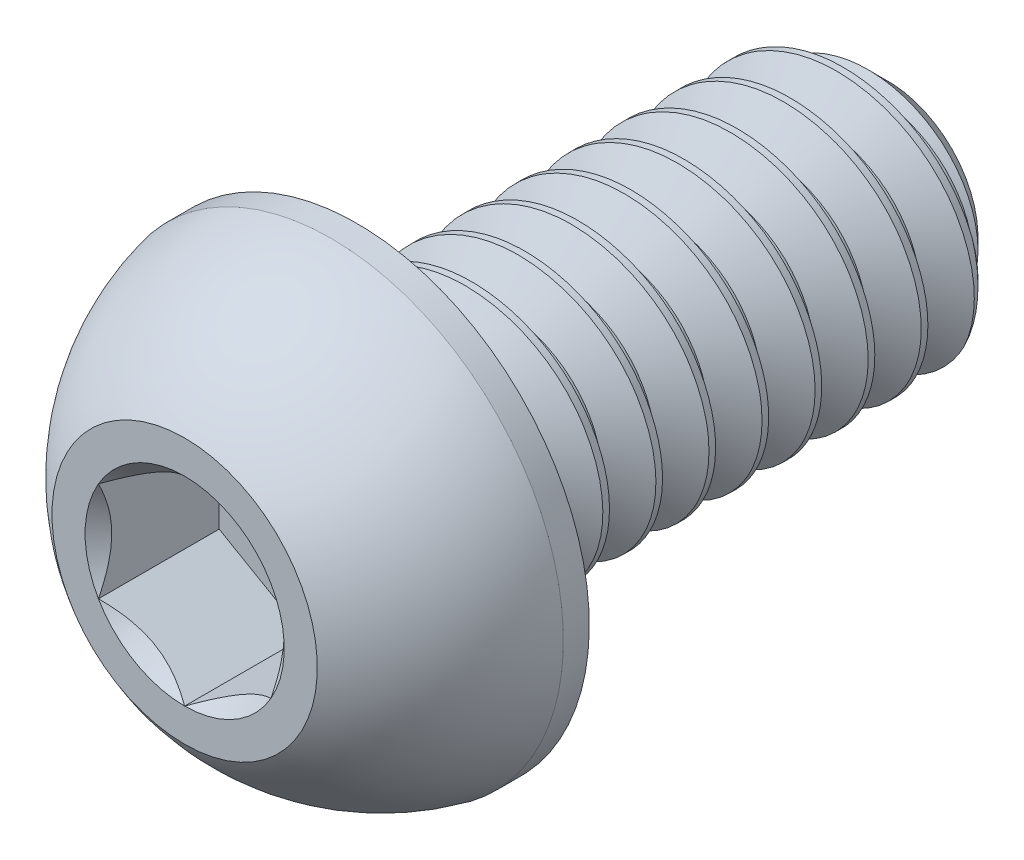
SolidWorks part; units mm, degrees
ref_plane "Front Plane" through (0, 0, 0) normal (0, 0, 1) x (1, 0, 0)
ref_plane "Top Plane" through (0, 0, 0) normal (0, 1, 0) x (1, 0, 0)
ref_plane "Right Plane" through (0, 0, 0) normal (1, 0, 0) x (0, 0, -1)
sketch "Sketch1" plane through (0, 0, 0) normal (1, 0, 0) x (0, 0, -1)
  line L0 (-2.65, 0) -> (2.65, 0) construction
  line L1 (-1.35, 1.75) -> (-1.35, -1.75) construction
  line L2 (2.65, 1) -> (2.65, -1) construction
  line L3 (2.625, 1.0433) -> (2.825, 0.6969) construction
  line L4 (2.825, 0.6969) -> (3.025, 1.0433) construction
  line L5 (3.025, 1.0433) -> (2.625, 1.0433) construction
  line L6 (2.65, 1) -> (3, 1) construction
  line L7 (2.825, 1.0433) -> (2.825, 1) construction
  line L8 (2.825, 1) -> (2.825, 0.7402) construction
  line L9 (2.825, 0.7402) -> (2.825, 0.6969) construction
  line L10 (2.8, 0.7402) -> (2.85, 0.7402)
  line L11 (2.6375, 1.0217) -> (3.0125, 1.0217)
  line L12 (2.85, 0.7402) -> (3.0125, 1.0217)
  line L13 (2.8, 0.7402) -> (2.6375, 1.0217)
  line L14 (-2.65, 0.65) -> (-2.65, -0.65) construction
  line L15 (2.65, 1) -> (-1.35, 1) construction
  point P3 (-1.35, 0)
  point P6 (-1.74, 0)
  point P21 (2.825, 1.0217)
  point P24 (-1.545, 1.75)
  point P25 (1.65, -1)
  point P26 (-2.65, 1)
  dimension "Head Height" = 1.3
  dimension "Length" = 4
  dimension "Head Dia" = 3.5
  dimension "Thread Dia" = 2
  dimension "Pitch" = 0.4
  dimension "D2" = 0.05
  dimension "Drive Size" = 1.3
  dimension "D1" = 0.91
  dimension "D3" = 0.195
  dimension "D4" = 1
sketch "Sketch2" plane through (0, 0, 0) normal (1, 0, 0) x (0, 0, -1)
  line L0 (-2.65, 0) -> (2.65, 0)
  line L1 (2.65, 0) -> (2.65, 0.68)
  line L2 (2.65, 1) -> (2.65, -1) construction
  line L3 (2.65, 0.68) -> (2.33, 1)
  line L4 (2.33, 1) -> (-1.35, 1)
  line L5 (-1.35, 1.75) -> (-1.35, -1.75) construction
  line L6 (-1.35, 1) -> (-1.35, 1.75)
  line L7 (-1.35, 1.75) -> (-1.545, 1.75)
  line L8 (2.65, 1) -> (3, 1) construction
  line L9 (-2.65, 0) -> (-2.65, 1)
  arc A0 (-2.65, 1) -> (-1.545, 1.75) centre (-1.1642, 0) cw
  dimension "D1" = 0.32
  dimension "D2" = 45
revolve "Revolve1" add sketch "Sketch2" angle 360 about L0
sketch "Sketch3" plane through (0, 0, 2.65) normal (0, 0, 1) x (1, 0, 0)
  line L1 (0, 0.7506) -> (-0.65, 0.3753)
  line L2 (-0.65, 0.3753) -> (-0.65, -0.3753)
  line L3 (-0.65, -0.3753) -> (0, -0.7506)
  line L4 (0, -0.7506) -> (0.65, -0.3753)
  line L5 (0.65, -0.3753) -> (0.65, 0.3753)
  line L6 (0.65, 0.3753) -> (0, 0.7506)
  circle A0 centre (0, 0) radius 0.65 construction
  dimension "D1" = 1.3
extrude "Cut-Extrude1" cut sketch "Sketch3" against normal up to vertex (0.91 mm away) up to point (0, 0, 1.74)
sketch "Sketch4" plane through (0, 0, 2.65) normal (0, 0, 1) x (1, 0, 0)
  circle A0 centre (0, 0) radius 0.7506
extrude "Cut-Extrude2" cut sketch "Sketch4" against normal blind 10 draft 45
split "Split1" bodies to split 106 resulting bodies 107 108 split by face at (0, -1.75, 1.35)
sketch "Sketch5" plane through (0, 0, -2.65) normal (0, 0, -1) x (-1, 0, 0)
  circle A0 centre (0, 0) radius 1 construction
  circle A1 centre (0, 0) radius 1
curve "Helix/Spiral1" pitch 0.4 height 4.4 radius 1 centre (0, 0, -2.65) axis (0, 0, 1) start towards (0, 1, 0)
sketch "Sketch6" plane through (0, 0, 0) normal (1, 0, 0) x (0, 0, -1)
  line L0 (2.8, 0.7402) -> (2.85, 0.7402) construction
  line L1 (2.8, 0.7402) -> (2.6375, 1.0217) construction
  line L2 (2.6375, 1.0217) -> (3.0125, 1.0217) construction
  line L3 (2.85, 0.7402) -> (3.0125, 1.0217) construction
  line L4 (2.8, 0.7402) -> (2.85, 0.7402)
  line L5 (2.8, 0.7402) -> (2.6375, 1.0217)
  line L6 (2.6375, 1.0217) -> (3.0125, 1.0217)
  line L7 (2.85, 0.7402) -> (3.0125, 1.0217)
sweep "Cut-Sweep1" cut profiles "Sketch6" path "Helix/Spiral1" align with end faces yes
sketch "Sketch7" plane through (0, 0, 1.35) normal (0, 0, -1) x (-1, 0, 0)
  circle A1 centre (0, 0) radius 1
  circle A2 centre (0, 0) radius 1
  dimension "D1" = 0
extrude "Boss-Extrude1" add sketch "Sketch7" along normal blind 10 draft 30
equation "\"D2@Sketch1\" = \"Pitch@Sketch1\" / 8"
equation "\"D1@Sketch1\"=\"Drive Size@Sketch1\"*.7"
equation "\"D3@Sketch1\"=\"Head Height@Sketch1\"*.15"
equation "\"D1@Sketch2\"=\"Pitch@Sketch1\"*.8"
equation "\"D1@Sketch3\"=\"Drive Size@Sketch1\""
equation "\"D4@Helix/Spiral1\"=\"Pitch@Sketch1\""
equation "\"D3@Helix/Spiral1\"=\"Length@Sketch1\"+\"Pitch@Sketch1\""
equation "\"D4@Sketch1\"=\"Pitch@Sketch1\"*2.5"
